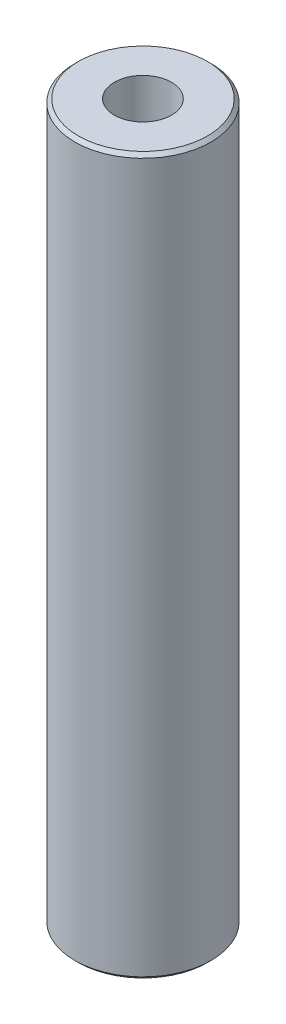
SolidWorks part; units mm, degrees
ref_plane "Front Plane" through (0, 0, 0) normal (0, 0, 1) x (1, 0, 0)
ref_plane "Top Plane" through (0, 0, 0) normal (0, 1, 0) x (1, 0, 0)
ref_plane "Right Plane" through (0, 0, 0) normal (1, 0, 0) x (0, 0, -1)
sketch "Sketch1" plane through (0, 0, 0) normal (0, 1, 0) x (1, 0, 0)
  circle A0 centre (0, 0) radius 15
  dimension "SHAFT_OD" = 30
extrude "Boss-Extrude1" add sketch "Sketch1" along normal blind 157.7463
sketch "Sketch2" plane through (0, 0, 0) normal (0, 1, 0) x (1, 0, 0)
  circle A0 centre (0, 0) radius 6.293
  dimension "BORE_D" = 12.586
extrude "Cut-Extrude1" cut sketch "Sketch2" along normal through all
chamfer "Chamfer1" distance 0.7752 angle 45 2 edges at (0, 157.7463, 15) (0, 0, 15)
